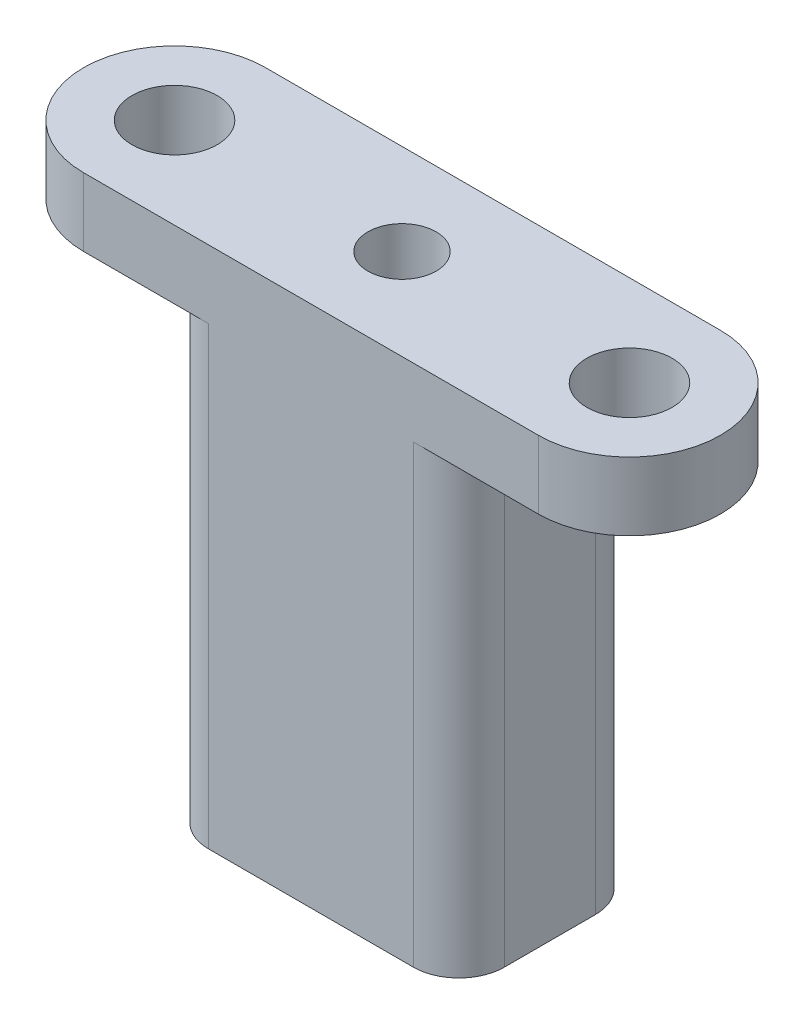
SolidWorks part; units mm, degrees
ref_plane "Front Plane" through (0, 0, 0) normal (0, 0, 1) x (1, 0, 0)
ref_plane "Top Plane" through (0, 0, 0) normal (0, 1, 0) x (1, 0, 0)
ref_plane "Right Plane" through (0, 0, 0) normal (1, 0, 0) x (0, 0, -1)
sketch "Sketch1" plane through (0, 0, 0) normal (0, 1, 0) x (1, 0, 0)
  line L1 (-10, -4) -> (10, -4)
  line L2 (-10, -4) -> (-10, 4) construction
  line L3 (-10, 4) -> (10, 4)
  line L4 (10, -4) -> (10, 4) construction
  line L5 (-10, -4) -> (10, 4) construction
  line L6 (-10, 4) -> (10, -4) construction
  arc A0 (-10, -4) -> (-10, 4) centre (-10, 0) cw
  arc A1 (10, -4) -> (10, 4) centre (10, 0) ccw
  circle A2 centre (-10, 0) radius 1.875
  circle A3 centre (10, 0) radius 1.875
  circle A4 centre (0, 0) radius 1.5
  point P0 (0, 0)
  dimension "D1" = 3.75
  dimension "D2" = 3
  dimension "D3" = 8
  dimension "D4" = 20
extrude "Boss-Extrude1" add sketch "Sketch1" along normal blind 3
sketch "Sketch3" plane through (0, 0, 0) normal (0, -1, 0) x (1, 0, 0)
  line L0 (-10, 4) -> (10, 4) construction
  line L1 (-6.5, -4) -> (6.5, -4)
  line L2 (-6.5, -4) -> (-6.5, 4)
  line L3 (-6.5, 4) -> (6.5, 4)
  line L4 (6.5, -4) -> (6.5, 4)
  line L5 (-6.5, -4) -> (6.5, 4) construction
  line L6 (-6.5, 4) -> (6.5, -4) construction
  circle A0 centre (0, 0) radius 1.5 construction
  circle A1 centre (0, 0) radius 1.5
  point P0 (0, 0)
  dimension "D1" = 13
extrude "Boss-Extrude2" add sketch "Sketch3" along normal blind 20
fillet "Fillet1" radius 2 4 edges at (-6.5, -10, 4) (6.5, -10, 4) (6.5, -10, -4) (-6.5, -10, -4)
